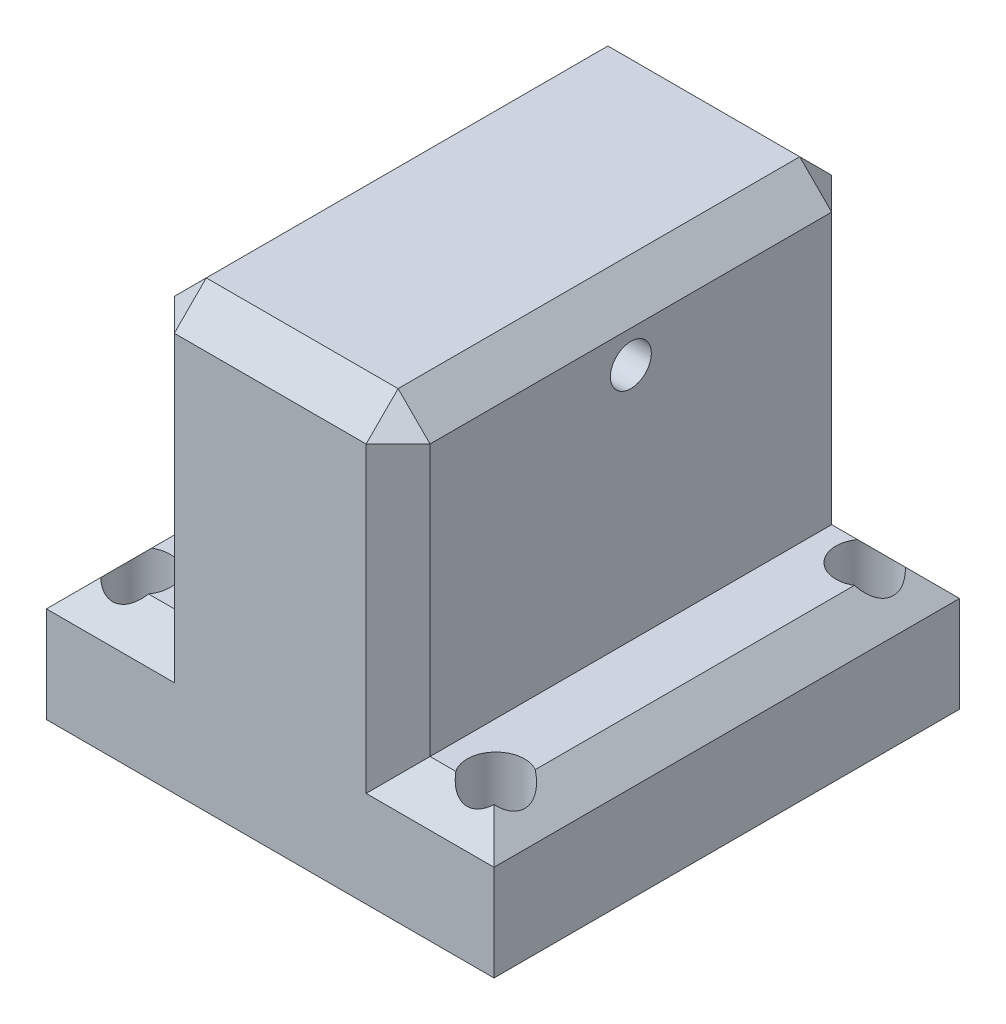
SolidWorks part; units mm, degrees
ref_plane "Front Plane" through (0, 0, 0) normal (0, 0, 1) x (1, 0, 0)
ref_plane "Top Plane" through (0, 0, 0) normal (0, 1, 0) x (1, 0, 0)
ref_plane "Right Plane" through (0, 0, 0) normal (1, 0, 0) x (0, 0, -1)
sketch "Sketch1" plane through (0, 0, 0) normal (0, 1, 0) x (1, 0, 0)
  line L0 (0, 0) -> (70, 72.813) construction
  line L1 (0, 0) -> (70, 0)
  line L2 (0, 0) -> (0, 72.813)
  line L3 (0, 72.813) -> (70, 72.813)
  line L4 (70, 0) -> (70, 72.813)
  line L5 (0, 72.813) -> (70, 0) construction
  line L6 (35, 72.813) -> (35, 0) construction
  line L7 (0, 36.4065) -> (70, 36.4065) construction
  circle A0 centre (62.7218, 65.2423) radius 2.6
  circle A1 centre (7.2782, 65.2423) radius 2.6
  circle A2 centre (62.7218, 7.5707) radius 2.6
  circle A3 centre (7.2782, 7.5707) radius 2.6
  point P4 (35, 36.4065)
  dimension "D3" = 40
  dimension "D4" = 5.2
  dimension "D1" = 72.813
  dimension "D2" = 70
extrude "Boss-Extrude1" add sketch "Sketch1" along normal blind 20
sketch "Sketch2" plane through (0, 20, 0) normal (0, 1, 0) x (1, 0, 0)
  circle A0 centre (62.7218, 65.2423) radius 4.5
  circle A1 centre (7.2782, 65.2423) radius 4.5
  circle A2 centre (7.2782, 7.5707) radius 4.5
  circle A3 centre (62.7218, 7.5707) radius 4.5
  dimension "D1" = 9
extrude "Cut-Extrude1" cut sketch "Sketch2" against normal blind 10
sketch "Sketch3" plane through (0, 20, 0) normal (0, 1, 0) x (1, 0, 0)
  line L0 (35, 72.813) -> (35, 0) construction
  line L1 (70, 72.813) -> (0, 72.813) construction
  line L2 (0, 0) -> (70, 0) construction
  line L4 (15, 72.813) -> (55, 72.813)
  line L5 (15, 72.813) -> (15, 0)
  line L6 (15, 0) -> (55, 0)
  line L7 (55, 72.813) -> (55, 0)
  line L8 (15, 72.813) -> (55, 0) construction
  line L9 (15, 0) -> (55, 72.813) construction
  point P6 (35, 36.4065)
  dimension "D1" = 40
extrude "Boss-Extrude2" add sketch "Sketch3" along normal blind 47.3282
sketch "Sketch5" plane through (55, 0, 0) normal (1, 0, 0) x (0, 0, -1)
  line L0 (36.4065, 0) -> (36.4065, 57.3282) construction
  line L1 (0, 0) -> (72.813, 0) construction
  circle A0 centre (36.4065, 57.3282) radius 3.2
  dimension "D2" = 6.4
  dimension "D1" = 57.3282
extrude "Cut-Extrude2" cut sketch "Sketch5" against normal blind 10
chamfer "Chamfer1" distance 5 angle 45 14 edges at (7.5, 20, -72.813) (62.5, 20, -72.813) (0, 20, -36.4065) (7.5, 20, 0) (70, 20, -36.4065) (62.5, 20, 0) (55, 43.6641, -72.813) (35, 67.3282, -72.813) (15, 43.6641, -72.813) (15, 67.3282, -36.4065) (15, 43.6641, 0) (35, 67.3282, 0) (55, 43.6641, 0) (55, 67.3282, -36.4065)
